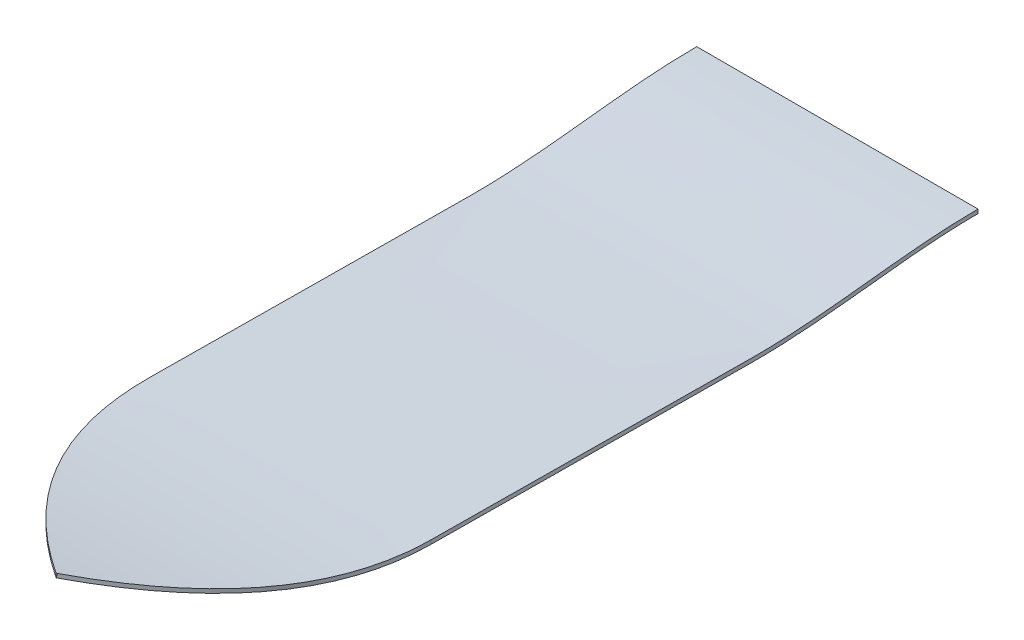
SolidWorks part; units mm, degrees
ref_plane "Front Plane" through (0, 0, 0) normal (0, 0, 1) x (1, 0, 0)
ref_plane "Top Plane" through (0, 0, 0) normal (0, 1, 0) x (1, 0, 0)
ref_plane "Right Plane" through (0, 0, 0) normal (1, 0, 0) x (0, 0, -1)
sketch "Sketch1" plane through (0, 0, 0) normal (1, 0, 0) x (0, 0, -1)
  line L0 (-2543.9836, 91.5006) -> (-2547.9286, 66.4088)
  line L1 (2455.2444, 60.7522) -> (2455.2444, 35.3522)
  spline S0 degree 3 poles (-2543.9836, 91.5006) (-2312.0356, 55.0337) (-1972.0739, 16.2277) (-1494.6551, -12.3936) (-1247.39, -19.826) (-1100.6392, -21.6769) (-1073.2398, -21.9434) (-1052.6732, -22.1295) (-953.2815, -23.04) (-775.0611, -24.6719) (-500.8746, -27.1814) (-199.2695, -29.942) (129.7543, -32.9535) (431.3594, -35.714) (705.546, -38.2237) (878.6277, -39.8094) (972.8766, -40.6694) (986.5876, -40.7965) (1005.396, -40.927) (1088.6934, -41.0221) (1233.8008, -36.7266) (1715.2391, -3.0184) (2093.6202, 60.7522) (2455.2444, 60.7522) knots 0 0 0 0 0.15625 0.21875 0.289062 0.300781 0.302734 0.304688 0.3125 0.359375 0.40625 0.46875 0.53125 0.59375 0.640625 0.6875 0.692383 0.694336 0.695312 0.703125 0.742188 0.78125 1 1 1 1
  spline S1 degree 1 poles (-2547.9286, 66.4088) (2455.2444, 35.3522) knots 0 0 1 1 construction
  spline S2 degree 3 poles (-2547.9286, 66.4088) (-2542.1057, 65.4933) (-2530.4663, 63.6765) (-2507.1126, 60.0835) (-2477.826, 55.6758) (-2442.5167, 50.5179) (-2395.2221, 43.8166) (-2335.6974, 35.7694) (-2263.6182, 26.64) (-2190.8892, 18.0375) (-2093.0508, 7.2702) (-1969.1282, -4.8719) (-1817.8215, -17.3355) (-1663.9148, -27.693) (-1507.4084, -35.945) (-1374.8182, -41.0667) (-1267.4485, -44.1136) (-1186.264, -45.8681) (-1118.0913, -46.9067) (-1063.1743, -47.4407) (-1008.3587, -47.9328) (-939.8022, -48.5656) (-830.1322, -49.5679) (-693.0371, -50.8239) (-528.5258, -52.3293) (-364.0138, -53.8352) (-199.5019, -55.3409) (-34.99, -56.8467) (129.5218, -58.3524) (294.0337, -59.8582) (458.5456, -61.3639) (595.6389, -62.6187) (705.3137, -63.623) (787.5702, -64.3763) (856.1169, -65.0039) (910.9542, -65.5048) (945.2262, -65.819) (969.2185, -66.0358) (982.9213, -66.1657) (996.7244, -66.2745) (1013.8622, -66.3363) (1041.1699, -66.3003) (1075.0353, -65.9984) (1128.694, -65.0008) (1194.8159, -62.8415) (1272.7896, -58.9668) (1349.5369, -53.9835) (1450.4277, -46.0944) (1574.212, -34.3366) (1720.2143, -18.5886) (1864.8758, -2.5902) (1985.3166, 9.8011) (2082.2125, 18.4647) (2155.3096, 24.1673) (2228.9862, 28.9047) (2290.9949, 31.9064) (2341.0474, 33.6554) (2378.827, 34.6196) (2410.5334, 35.1159) (2436.0269, 35.3179) (2448.8444, 35.3522) (2455.2444, 35.3522) knots 0 0 0 0 0.003906 0.007812 0.015625 0.023438 0.03125 0.046875 0.0625 0.078125 0.09375 0.125 0.15625 0.1875 0.21875 0.25 0.265625 0.28125 0.296875 0.304688 0.3125 0.328125 0.34375 0.375 0.40625 0.4375 0.46875 0.5 0.53125 0.5625 0.59375 0.625 0.640625 0.65625 0.671875 0.679688 0.6875 0.691406 0.693359 0.695312 0.699219 0.703125 0.710938 0.71875 0.734375 0.75 0.765625 0.78125 0.8125 0.84375 0.875 0.90625 0.921875 0.9375 0.953125 0.96875 0.976562 0.984375 0.992188 0.996094 1 1 1 1
  dimension "D1" = 25.4
extrude "Boss-Extrude1" add sketch "Sketch1" along normal blind 1524 and the other way blind 1524
sketch "Sketch3" plane through (0, 0, 0) normal (0, 1, 0) x (1, 0, 0)
  line L0 (-900, 2451.2897) -> (900, 2451.2897)
  line L1 (-900, 2451.2897) -> (-900, -1047.9383)
  line L2 (900, 2451.2897) -> (900, -1047.9383)
  line L4 (-1976.5237, 2801.7222) -> (3754.9336, 2801.7222)
  line L5 (-1976.5237, 2801.7222) -> (-1976.5237, -4542.2553)
  line L6 (-1976.5237, -4542.2553) -> (3754.9336, -4542.2553)
  line L7 (3754.9336, 2801.7222) -> (3754.9336, -4542.2553)
  spline S0 degree 2 poles (-900, -1047.9383) (-900, -1922.5769) (0, -2547.9286) knots 0 0 0 1 1 1
  spline S1 degree 2 poles (900, -1047.9383) (900, -1922.5769) (0, -2547.9286) knots 0 0 0 1 1 1
  dimension "D1" = 1800
extrude "Cut-Extrude1" cut sketch "Sketch3" against normal through all both and the other way through all
